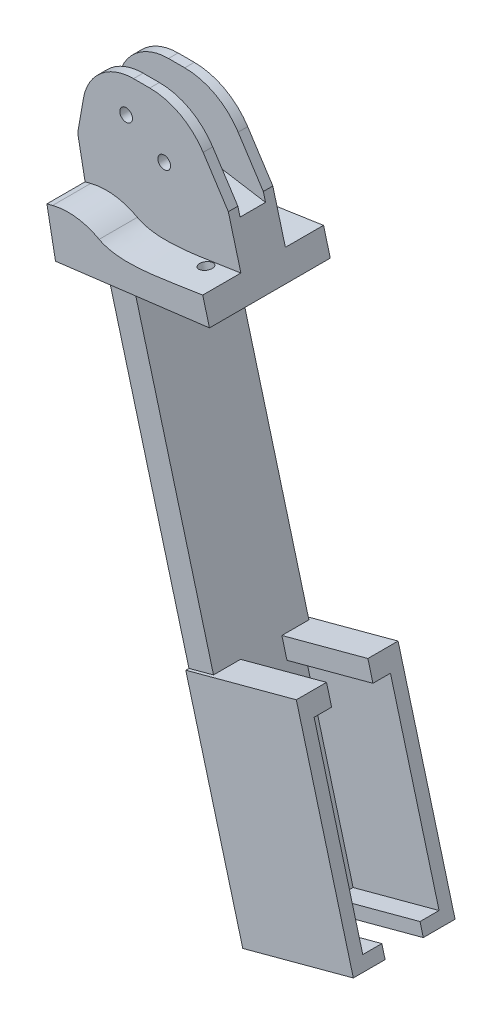
SolidWorks part; units mm, degrees
ref_plane "Спереди" through (0, 0, 0) normal (0, 0, 1) x (1, 0, 0)
ref_plane "Сверху" through (0, 0, 0) normal (0, 1, 0) x (1, 0, 0)
ref_plane "Справа" through (0, 0, 0) normal (1, 0, 0) x (0, 0, -1)
sketch "Sketch5" plane through (0, 0, 0) normal (0, 0, 1) x (1, 0, 0)
  line L0 (1.7523, 0.4742) -> (37.3029, 86.8114) construction
  line L1 (-1.0106, -0.6044) -> (29.6618, 87.5839) construction
  line L2 (0, 0) -> (17.8901, 43.1295)
  line L3 (0, 0) -> (114.3643, 0) construction
  line L4 (23.8823, 39.6684) -> (24.5035, 51.2503)
  line B0 (17.4507, 115.16) -> (29.9551, 112.6983)
  spline B1 degree 3 poles (29.9551, 112.6983) (28.321, 116.0983) (27.9284, 121.1676) (30.1713, 134.4746) (29.8473, 132.0116) (30.6222, 139.9349) (27.0176, 140.9027) knots 0 0 0 0 0.297085 0.369784 0.687298 1 1 1 1
  spline B2 degree 2 poles (27.0176, 140.9027) (20.5603, 128.6427) (17.4507, 115.16) knots 0 0 0 1 1 1
  spline B3 degree 2 poles (27.0176, 140.9027) (26.5004, 134.6878) (22.2537, 130.5645) knots 0 0 0 1 1 1
  line B4 (17.1977, 114.3508) -> (29.842, 112.2111)
  line B5 (28.7001, 84.8969) -> (10.3668, 87.513)
  spline B6 degree 1 poles (17.1977, 114.3508) (10.3668, 87.513) knots 0 0 1 1
  spline B7 degree 2 poles (29.842, 112.2111) (22.5534, 98.8452) (28.7001, 84.8969) knots 0 0 0 1 1 1
  line B8 (10.1904, 87.4159) -> (28.2572, 84.4958)
  line B9 (32.8909, 45.7292) -> (10.0695, 42.8593)
  spline B10 degree 2 poles (10.1904, 87.4159) (10.0234, 65.1379) (10.0695, 42.8593) knots 0 0 0 1 1 1
  spline B11 degree 2 poles (28.2572, 84.4958) (20.6417, 64.1094) (32.8909, 45.7292) knots 0 0 0 1 1 1
  line B12 (10.2797, 36.8758) -> (3.9253, -13.9853)
  line B13 (3.9253, -13.9853) -> (33.9594, -31.0804)
  line B14 (33.9594, -31.0804) -> (45.9193, -27.7969)
  line B15 (45.9193, -27.7969) -> (58.2918, -13.9853)
  line B16 (58.2918, -13.9853) -> (69.0331, -4.9875)
  line B17 (69.0331, -4.9875) -> (82.514, 2.0236)
  line B18 (82.514, 2.0236) -> (89.2736, 3.8794)
  line B19 (89.2736, 3.8794) -> (92.4846, 9.5208)
  line B20 (92.4846, 9.5208) -> (96.8914, 17.263)
  line B21 (96.8914, 17.263) -> (101.4978, 21.1217)
  line B22 (101.4978, 21.1217) -> (103.9241, 23.1541)
  line B23 (104.261, 27.4157) -> (104.5375, 25.5318)
  line B24 (84.192, 21.2056) -> (87.7484, 22.7822)
  line B25 (87.7484, 22.7822) -> (92.912, 27.4956)
  line B26 (71.6086, 15.6268) -> (84.192, 21.2056)
  line B27 (92.912, 27.4956) -> (95.357, 29.7274)
  line B28 (95.357, 29.7274) -> (96.8049, 29.9399)
  line B29 (71.6086, 15.6268) -> (53.4239, 15.2713)
  line B30 (48.0904, 17.5622) -> (39.9394, 26.4919)
  line B31 (39.9394, 26.4919) -> (33.9594, 37.99)
  line B32 (33.9594, 37.99) -> (10.2797, 36.8758)
  line B33 (96.8049, 29.9399) -> (99.4078, 30.2175)
  line B34 (99.4078, 30.2175) -> (102.2786, 29.261)
  line B35 (102.2786, 29.261) -> (104.261, 27.4157)
  line B36 (104.5375, 25.5318) -> (103.9241, 23.1541)
  arc B37 (53.4239, 15.2713) -> (48.0904, 17.5622) centre (53.2864, 22.3051) cw
  spline B38 degree 3 poles (104.261, 27.4157) (103.5289, 27.0494) (99.8378, 26.2685) (94.8982, 17.2338) (98.6516, 18.7375) knots 0 0 0 0 0.441207 1 1 1 1
  line B39 (27.7375, 116.5129) -> (14.1959, 87.8955)
  line B40 (27.7375, 116.5129) -> (25.9485, 114.8372)
  line B41 (25.9485, 114.8372) -> (27.5763, 114.067)
  line B42 (27.7375, 116.5129) -> (27.5763, 114.067)
  line B43 (26.1527, 88.0864) -> (17.8901, 43.1295)
  line B44 (19.3622, 85.005) -> (23.8823, 39.6684)
  line B45 (19.3622, 85.005) -> (17.7584, 73.9508)
  line B46 (17.7584, 73.9508) -> (23.117, 74.485)
  line B47 (23.117, 74.485) -> (19.3622, 85.005)
  line B48 (26.1527, 88.0864) -> (23.7481, 82.7635)
  line B49 (23.7481, 82.7635) -> (25.1278, 82.5099)
  line B50 (25.1278, 82.5099) -> (26.5087, 82.2561)
  line B51 (26.5087, 82.2561) -> (26.1527, 88.0864)
  line B52 (26.1527, 88.0864) -> (19.3622, 85.005)
  line B53 (19.3622, 85.005) -> (22.3683, 87.7853)
  line B54 (22.3683, 87.7853) -> (22.9012, 86.6109)
  line B55 (22.9012, 86.6109) -> (23.4998, 85.2917)
  line B56 (23.4998, 85.2917) -> (19.3622, 85.005)
  dimension "D1" = 93.37
  dimension "D2" = 93.37
  dimension "D4" = 67.471
  dimension "D5" = 8.764
sketch_block_instance "Block1-1"
sketch_block "Block1"
sketch_block_instance "Block2-1"
sketch_block "Block2"
sketch_block_instance "Block3-1"
sketch_block "Block3"
sketch_block_instance "Block18-1"
sketch_block "Block18"
sketch_block_instance "Block44-1"
sketch_block "Block44"
sketch_block_instance "Block46-1"
sketch_block "Block46"
sketch_block_instance "Block47-1"
sketch_block "Block47"
sketch_block_instance "Block48-1"
sketch_block "Block48"
sketch_block_instance "Block50-1"
sketch_block "Block50"
sketch "Sketch10" plane through (0, 0, 0) normal (0, 0, 1) x (1, 0, 0)
  line L0 (27.0489, 48.6569) -> (33.9594, 37.99)
  line L3 (33.9594, 37.99) -> (36.9938, 26.6828)
  line L21 (10.2797, 36.8758) -> (12.7888, 23.6588)
  line L22 (12.7888, 23.6588) -> (36.9938, 26.6828)
  line L23 (10.2797, 36.8758) -> (12.3218, 48.6569)
  line L24 (12.3218, 48.6569) -> (27.0489, 48.6569)
  circle A0 centre (17.8901, 43.1295) radius 1
  circle A1 centre (23.8823, 39.6684) radius 1
  dimension "D1" = 2
extrude "Boss-Extrude5" add sketch "Sketch10" along normal mid plane 15
sketch "Sketch11" plane through (0, 0, 7.5) normal (0, 0, 1) x (1, 0, 0)
  line L0 (17.8254, 32.4239) -> (9.1239, 30.2079)
  line L1 (37.7529, 30.846) -> (34.6935, 60.2717)
  line L2 (34.6935, 60.2717) -> (6.5943, 53.1599)
  line L3 (6.5943, 53.1599) -> (9.1239, 30.2079)
  line L4 (37.7529, 30.846) -> (30.6791, 30.1551) construction
  line L5 (30.6791, 30.1551) -> (19.269, 26.7342) construction
  line L6 (19.269, 26.7342) -> (17.8254, 32.4239) construction
  line L7 (12.3218, 48.6569) -> (10.2797, 36.8758) construction
  spline S1 degree 3 poles (37.7529, 30.846) (30.6791, 30.1551) (19.269, 26.7342) (17.8254, 32.4239) knots 0 0 0 0 1 1 1 1
extrude "Cut-Extrude1" cut sketch "Sketch11" against normal blind 4
fillet "Fillet1" radius 10 1 edges at (27.0489, 48.6569, -2)
extrude "Cut-Extrude6" cut sketch "Sketch11<2>" against normal blind 10 from offset 11 offset against normal yes
sketch "Sketch11<2>" plane through (0, 0, 7.5) normal (0, 0, 1) x (1, 0, 0) same geometry as "Sketch11"
sketch "Sketch16" plane through (0, 0, 0) normal (0, 0, 1) x (1, 0, 0)
  line L1 (10.0743, 54.3608) -> (34.4186, 54.3608)
  line L2 (10.0743, 54.3608) -> (10.0743, 40.6451)
  line L3 (10.0743, 40.6451) -> (34.4186, 36.6644)
  line L4 (34.4186, 54.3608) -> (34.4186, 36.6644)
extrude "Cut-Extrude7" cut sketch "Sketch16" against normal mid plane 4
sketch "Sketch26" plane through (41.1882, 11.0532, 0) normal (0.9658, 0.2592, 0) x (0, 0, -1)
  line L12 (2, 27.8898) -> (2, 26.5356)
  line L13 (2, 26.5356) -> (-2, 26.5356)
  line L14 (-2, 26.5356) -> (-2, 27.8898)
  line L15 (-2, 27.8898) -> (-3.5, 27.8898)
  line L16 (-3.5, 27.8898) -> (-3.5, 20.2671)
  line L17 (-3.5, 20.2671) -> (-7.5, 20.2671)
  line L18 (-7.5, 20.2671) -> (-7.5, 16.1826)
  line L19 (-7.5, 16.1826) -> (7.5, 16.1826)
  line L20 (7.5, 16.1826) -> (7.5, 20.2671)
  line L21 (7.5, 20.2671) -> (3.5, 20.2671)
  line L22 (3.5, 20.2671) -> (3.5, 27.8898)
  line L23 (3.5, 27.8898) -> (2, 27.8898)
  line L24 (2, 27.8898) -> (2, 26.5356)
  line L25 (2, 26.5356) -> (-2, 26.5356)
  line L26 (-2, 26.5356) -> (-2, 27.8898)
  line L27 (-2, 27.8898) -> (-3.5, 27.8898)
  line L28 (-3.5, 27.8898) -> (-3.5, 20.2671)
  line L29 (-3.5, 20.2671) -> (-7.5, 20.2671)
  line L30 (-7.5, 20.2671) -> (-7.5, 16.1826)
  line L31 (-7.5, 16.1826) -> (7.5, 16.1826)
  line L32 (7.5, 16.1826) -> (7.5, 20.2671)
  line L33 (7.5, 20.2671) -> (3.5, 20.2671)
  line L34 (3.5, 20.2671) -> (3.5, 27.8898)
  line L35 (3.5, 27.8898) -> (2, 27.8898)
  dimension "D1" = 0
extrude "Boss-Extrude11" add sketch "Sketch26" along normal blind 9
sketch "Sketch28" plane through (-4.1944, 15.6296, 0) normal (0.2592, -0.9658, 0) x (0.9658, 0.2592, 0)
  line L0 (38.2441, 4.6151) -> (38.2441, -4.6151) construction
  line L1 (51.6455, 0) -> (42.6455, 0) construction
  line L2 (51.6455, 7.5) -> (51.6455, -7.5) construction
  line L3 (42.6455, 7.5) -> (42.6455, -7.5) construction
  circle A0 centre (38.2441, 4.6151) radius 1
  circle A1 centre (38.2441, -4.6151) radius 1
  point P10 (38.2441, 0)
  dimension "D1" = 2
extrude "Cut-Extrude8" cut sketch "Sketch28" against normal blind 9
sketch "Sketch30" plane through (-4.1944, 15.6296, 0) normal (0.2592, -0.9658, 0) x (0.9658, 0.2592, 0)
  line L0 (51.6455, 7.5) -> (42.6455, 7.5) construction
  line L1 (51.6455, 7.5) -> (26.6455, 7.5)
  line L2 (51.6455, 7.5) -> (51.6455, -7.5)
  line L3 (51.6455, -7.5) -> (26.6455, -7.5)
  line L4 (26.6455, 7.5) -> (26.6455, -7.5)
  line L5 (18.4838, -7.5) -> (42.6455, -7.5) construction
  line L6 (51.6455, 7.5) -> (51.6455, -7.5) construction
  line L7 (51.6455, -7.5) -> (42.6455, -7.5) construction
  line L9 (28.6455, 7.5) -> (26.6455, 7.5)
  line L10 (28.6455, 7.5) -> (28.6455, -7.5)
  line L11 (28.6455, -7.5) -> (26.6455, -7.5)
  line L12 (26.6455, 7.5) -> (26.6455, -7.5)
  line L13 (26.6455, 7.5) -> (24.6455, 7.5)
  line L14 (26.6455, 7.5) -> (26.6455, -7.5)
  line L15 (26.6455, -7.5) -> (24.6455, -7.5)
  line L16 (24.6455, 7.5) -> (24.6455, -7.5)
  dimension "D1" = 25
  dimension "D2" = 2
  dimension "D3" = 2
extrude "Boss-Extrude13" add sketch "Sketch30" along normal blind 80 and the other way blind 3 contours L10 L1 L4 L3 | L13 L16 L15 L4 region at (22.5064, 22.795, 0) region at (20.5748, 22.2766, 0)
sketch "Sketch31" plane through (27.6666, 7.4246, 0) normal (0.9658, 0.2592, 0) x (0, 0, -1)
  line L0 (-7.5, 16.1826) -> (7.5, 16.1826) construction
  line L1 (-6, -33.8174) -> (-3.25, -33.8174)
  line L2 (-6, -33.8174) -> (-6, -63.3174)
  line L3 (-6, -63.3174) -> (-3, -63.3174)
  line L4 (6, -33.8174) -> (6, -63.3174)
  line L5 (0, 0) -> (0, -17.1237) construction
  line L6 (0, -17.1237) -> (0, -50.3713) construction
  line L7 (-6, -33.8174) -> (-8, -33.8174)
  line L8 (-6, -33.8174) -> (-6, -63.3174)
  line L9 (-6, -63.3174) -> (-8, -63.3174)
  line L10 (-8, -33.8174) -> (-8, -63.3174)
  line L11 (6, -33.8174) -> (8, -33.8174)
  line L12 (6, -33.8174) -> (6, -63.3174)
  line L13 (6, -63.3174) -> (8, -63.3174)
  line L14 (8, -33.8174) -> (8, -63.3174)
  line L15 (-8, -33.8174) -> (-3.25, -33.8174)
  line L16 (-8, -33.8174) -> (-8, -30.7312)
  line L17 (-8, -30.7312) -> (-3.25, -30.7312)
  line L18 (8, -33.8174) -> (8, -30.7312)
  line L19 (8, -63.3174) -> (3, -63.3174)
  line L20 (8, -63.3174) -> (8, -65.3174)
  line L21 (8, -65.3174) -> (3, -65.3174)
  line L22 (-8, -63.3174) -> (-8, -65.3174)
  line L23 (-3.25, -33.8174) -> (-3.25, -30.7312)
  line L24 (3.25, -33.8174) -> (3.25, -30.7312)
  line L25 (3.25, -30.7312) -> (8, -30.7312)
  line L26 (3.25, -33.8174) -> (6, -33.8174)
  line L27 (3.25, -33.8174) -> (8, -33.8174)
  line L28 (-3, -63.3174) -> (-3, -65.3174)
  line L29 (3, -63.3174) -> (3, -65.3174)
  line L30 (-3, -65.3174) -> (-8, -65.3174)
  line L31 (3, -63.3174) -> (6, -63.3174)
  line L32 (-3, -63.3174) -> (-8, -63.3174)
  line L33 (-3.25, -17.1237) -> (3.25, -17.1237) construction
  line L34 (-3, -50.3713) -> (3, -50.3713) construction
  point P4 (0, -17.1237)
  point P20 (0, -17.1237)
  point P21 (5.5, -65.3174)
  point P29 (0, -17.1237)
  point P34 (0, -50.3713)
  point P35 (5.5, -63.3174)
  line M4 (7.5, -63.8174) -> (7.5, 18.1255)
  line M6 (-7.5, 18.1255) -> (-7.5, -63.8174)
  line M7 (-7.5, -63.8174) -> (7.5, -63.8174)
  dimension "D1" = 12
  dimension "D2" = 50
  dimension "D3" = 29.5
  dimension "D4" = 6
  dimension "D5" = 2
  dimension "D6" = 2
  dimension "D7" = 2
  dimension "D8" = 6.5
extrude "Boss-Extrude14" add sketch "Sketch31" along normal blind 14 and the other way blind 4 contours L9 L2 L7 M6 | L7 L10 L9 M6 | L4 L13 L11 M4 | L14 L11 L13 M4 | L28 L3 L9 M6 M7 | L29 L21 L20 L13 M7 M4 | L19 L29 L13 M7 M4 | L30 L28 L9 L22 M7 M6 | L1 L23 L17 L7 M6 | L24 L26 L11 L25 M4 | L25 L11 L18 M4 | L17 L16 L7 M6 region at (36.0317, -23.7468, 5.375) region at (44.1426, -53.9705, -5.25) region at (44.3934, -54.9052, -5.5726) region at (40.2547, -39.4831, 6.75) region at (44.1426, -53.9705, 5.25) region at (40.2547, -39.4831, 7.75) region at (36.0317, -23.7468, 7.75) region at (44.3934, -54.9052, 5.5726) region at (40.2547, -39.4831, -6.75) region at (40.2547, -39.4831, -7.75) region at (36.0317, -23.7468, -5.375) region at (36.0317, -23.7468, -7.75)
sketch "Sketch32" plane through (49.8806, 13.3859, 0) normal (0.9658, 0.2592, 0) x (0, 0, -1)
  line L12 (3.5, 27.8898) -> (2, 27.8898)
  line L13 (2, 27.8898) -> (2, 26.5356)
  line L14 (2, 26.5356) -> (-2, 26.5356)
  line L15 (-2, 26.5356) -> (-2, 27.8898)
  line L16 (-2, 27.8898) -> (-3.5, 27.8898)
  line L17 (-3.5, 27.8898) -> (-3.5, 20.2671)
  line L18 (-3.5, 20.2671) -> (-7.5, 20.2671)
  line L19 (-7.5, 20.2671) -> (-7.5, 16.1826)
  line L20 (-7.5, 16.1826) -> (7.5, 16.1826)
  line L21 (7.5, 16.1826) -> (7.5, 20.2671)
  line L22 (7.5, 20.2671) -> (3.5, 20.2671)
  line L23 (3.5, 20.2671) -> (3.5, 27.8898)
  line L24 (3.5, 27.8898) -> (2, 27.8898)
  line L25 (2, 27.8898) -> (2, 26.5356)
  line L26 (2, 26.5356) -> (-2, 26.5356)
  line L27 (-2, 26.5356) -> (-2, 27.8898)
  line L28 (-2, 27.8898) -> (-3.5, 27.8898)
  line L29 (-3.5, 27.8898) -> (-3.5, 20.2671)
  line L30 (-3.5, 20.2671) -> (-7.5, 20.2671)
  line L31 (-7.5, 20.2671) -> (-7.5, 16.1826)
  line L32 (-7.5, 16.1826) -> (7.5, 16.1826)
  line L33 (7.5, 16.1826) -> (7.5, 20.2671)
  line L34 (7.5, 20.2671) -> (3.5, 20.2671)
  line L35 (3.5, 20.2671) -> (3.5, 27.8898)
  dimension "D1" = 0
extrude "Cut-Extrude9" cut sketch "Sketch32" against normal blind 9
fillet "Fillet2" radius 8 2 edges at (12.3218, 48.6569, 2.75) (12.3218, 48.6569, -2.75)
fillet "Fillet3" radius 10 2 edges at (17.8254, 32.4239, 5.5) (17.8254, 32.4239, -5.5)
sketch "Sketch33" plane through (0, 0, -7.5) normal (0, 0, -1) x (-1, 0, 0)
  line L8 (-11.4338, 30.7962) -> (-12.3264, 31.0235)
  line L9 (-35.9352, 30.6278) -> (-36.9938, 26.6828)
  line L10 (-36.9938, 26.6828) -> (-22.9687, 24.9306)
  line L11 (-22.9687, 24.9306) -> (-35.6318, -22.2564)
  line L12 (-35.6318, -22.2564) -> (-31.7685, -23.2931)
  line L13 (-31.7685, -23.2931) -> (-18.9615, 24.43)
  line L14 (-18.9615, 24.43) -> (-12.7888, 23.6588)
  line L15 (-12.7888, 23.6588) -> (-11.4338, 30.7962)
  line L16 (-11.4338, 30.7962) -> (-12.3264, 31.0235)
  line L17 (-35.9352, 30.6278) -> (-36.9938, 26.6828)
  line L18 (-36.9938, 26.6828) -> (-22.9687, 24.9306)
  line L22 (-22.9687, 24.9306) -> (-12.7888, 23.6588)
  line L23 (-12.7888, 23.6588) -> (-11.4338, 30.7962)
  arc A1 (-12.3264, 31.0235) -> (-19.6523, 30.0735) centre (-14.7943, 21.3328) ccw
  arc A2 (-12.3264, 31.0235) -> (-19.6523, 30.0735) centre (-14.7943, 21.3328) ccw
  spline S1 degree 3 poles (-1492.9435, 1381.8324) (1613.9049, -1324.9598) (-1698.3177, 1362.6042) (1495.4653, -1255.4074) knots -4.104663 -4.104663 -4.104663 -4.104663 5.56333 5.56333 5.56333 5.56333 only from (-19.6523, 30.0735) to (-35.9352, 30.6278)
  spline S2 degree 3 poles (-19.6523, 30.0735) (-23.0942, 28.1606) (-30.3498, 29.8586) (-35.9352, 30.6278) knots 0.191604 0.191604 0.191604 0.191604 0.918086 0.918086 0.918086 0.918086
  dimension "D1" = 0
extrude "Boss-Extrude15" add sketch "Sketch33" along normal blind 2
sketch "Sketch34" plane through (0, 0, 7.5) normal (0, 0, 1) x (1, 0, 0)
  line L8 (12.3264, 31.0235) -> (11.4338, 30.7962)
  line L9 (11.4338, 30.7962) -> (12.7888, 23.6588)
  line L10 (12.7888, 23.6588) -> (18.9615, 24.43)
  line L11 (18.9615, 24.43) -> (31.7685, -23.2931)
  line L12 (31.7685, -23.2931) -> (35.6318, -22.2564)
  line L13 (35.6318, -22.2564) -> (22.9687, 24.9306)
  line L14 (22.9687, 24.9306) -> (36.9938, 26.6828)
  line L15 (36.9938, 26.6828) -> (35.9352, 30.6278)
  line L16 (12.3264, 31.0235) -> (11.4338, 30.7962)
  line L17 (11.4338, 30.7962) -> (12.7888, 23.6588)
  line L18 (12.7888, 23.6588) -> (22.9687, 24.9306)
  line L22 (22.9687, 24.9306) -> (36.9938, 26.6828)
  line L23 (36.9938, 26.6828) -> (35.9352, 30.6278)
  arc A1 (19.6523, 30.0735) -> (12.3264, 31.0235) centre (14.7943, 21.3328) ccw
  arc A2 (19.6523, 30.0735) -> (12.3264, 31.0235) centre (14.7943, 21.3328) ccw
  spline S1 degree 3 poles (-1495.5224, -1255.4542) (1698.3569, 1362.636) (-1613.9228, -1324.9754) (1492.9426, 1381.8317) knots -4.453698 -4.453698 -4.453698 -4.453698 5.214352 5.214352 5.214352 5.214352 only from (35.9352, 30.6278) to (19.6523, 30.0735)
  spline S2 degree 3 poles (35.9352, 30.6278) (30.3498, 29.8586) (23.0942, 28.1606) (19.6523, 30.0735) knots 0.191604 0.191604 0.191604 0.191604 0.918086 0.918086 0.918086 0.918086
  dimension "D1" = 0
extrude "Boss-Extrude16" add sketch "Sketch34" along normal blind 2
